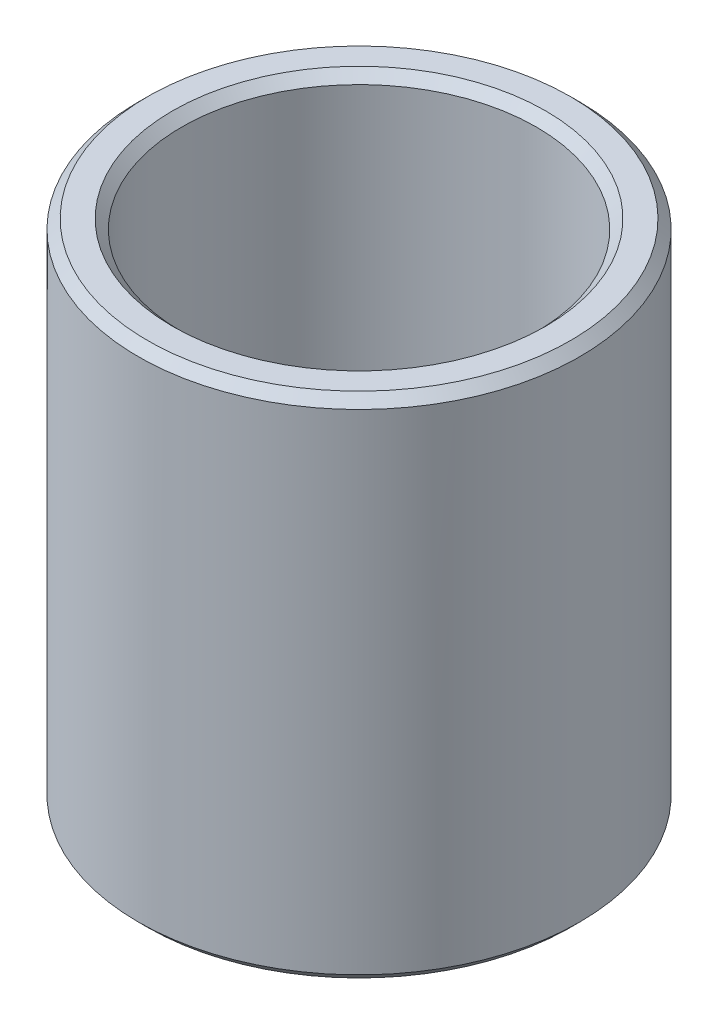
SolidWorks part; units mm, degrees
ref_plane "Front Plane" through (0, 0, 0) normal (0, 0, 1) x (1, 0, 0)
ref_plane "Top Plane" through (0, 0, 0) normal (0, 1, 0) x (1, 0, 0)
ref_plane "Right Plane" through (0, 0, 0) normal (1, 0, 0) x (0, 0, -1)
sketch "Sketch1" plane through (0, 0, 0) normal (0, 1, 0) x (1, 0, 0)
  circle A0 centre (0, 0) radius 32.5
  dimension "SLEEVE_OD" = 65
extrude "Boss-Extrude1" add sketch "Sketch1" along normal blind 74.8433
sketch "Sketch2" plane through (0, 0, 0) normal (0, 1, 0) x (1, 0, 0)
  circle A0 centre (0, 0) radius 26.1104
  dimension "BORE_D" = 52.2207
extrude "Cut-Extrude1" cut sketch "Sketch2" along normal through all
chamfer "Chamfer1" distance 1.3705 angle 45 4 edges at (0, 74.8433, 26.1104) (0, 0, 26.1104) (0, 0, 32.5) (0, 74.8433, 32.5)
